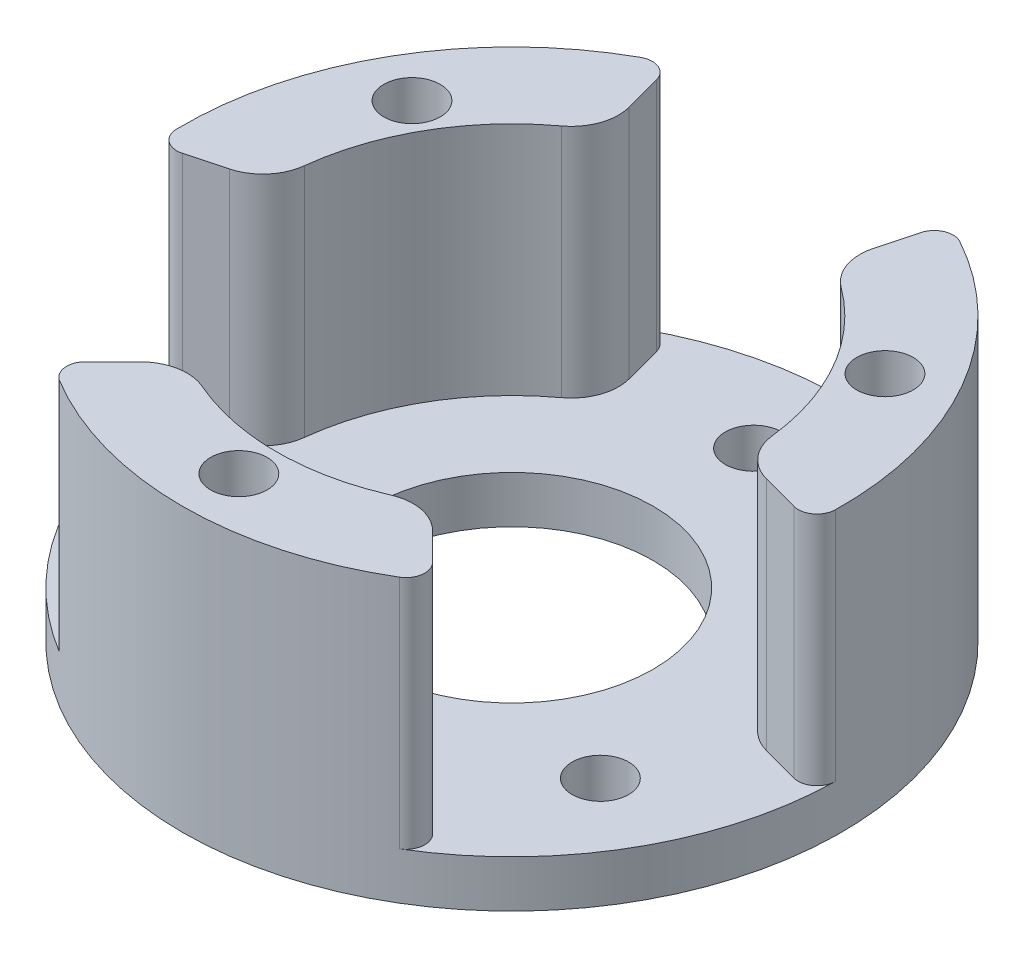
SolidWorks part; units mm, degrees
ref_plane "Front Plane" through (0, 0, 0) normal (0, 0, 1) x (1, 0, 0)
ref_plane "Top Plane" through (0, 0, 0) normal (0, 1, 0) x (1, 0, 0)
ref_plane "Right Plane" through (0, 0, 0) normal (1, 0, 0) x (0, 0, -1)
sketch "Sketch1" plane through (0, 0, 0) normal (0, 1, 0) x (1, 0, 0)
  line L0 (0, 25.66) -> (0, 0) construction
  line L1 (22.2222, -12.83) -> (0, 0) construction
  line L2 (-22.2222, -12.83) -> (0, 0) construction
  circle A0 centre (0, 0) radius 25.66 construction
  circle A1 centre (0, 0) radius 35
  circle A2 centre (0, 25.66) radius 3
  circle A3 centre (22.2222, -12.83) radius 3
  circle A4 centre (-22.2222, -12.83) radius 3
  circle A5 centre (0, 0) radius 15
  point P3 (0, 25.66)
  point P7 (22.2222, -12.83)
  point P9 (-22.2222, -12.83)
  point P11 (0, 0)
  point P18 (0, 0)
  dimension "D3" = 70
  dimension "D4" = 6
  dimension "D6" = 30
  dimension "D2" = 25.66
  dimension "D1" = 3
  dimension "D5" = 3
extrude "Boss-Extrude1" add sketch "Sketch1" along normal blind 5
sketch "Sketch2" plane through (0, 5, 0) normal (0, -1, 0) x (1, 0, 0)
  line L0 (0, 0) -> (0, 35) construction
  line L1 (15.5355, 23.9599) -> (20.1755, 28.5998)
  line L2 (-15.5355, 23.9599) -> (-20.1755, 28.5998)
  line L3 (28.5177, 1.4742) -> (34.8559, 3.1725)
  line L4 (12.9821, -25.4341) -> (14.6805, -31.7724)
  line L5 (-12.9821, -25.4341) -> (-14.6805, -31.7724)
  line L6 (-28.5177, 1.4742) -> (-34.8559, 3.1725)
  circle A0 centre (0, 0) radius 35 construction
  arc A1 (-20.1755, 28.5998) -> (20.1755, 28.5998) centre (0, 0) cw
  arc A2 (-10, 22.9129) -> (10, 22.9129) centre (0, 0) cw
  arc A3 (10, 22.9129) -> (15.5355, 23.9599) centre (12, 27.4955) ccw
  arc A4 (-10, 22.9129) -> (-15.5355, 23.9599) centre (-12, 27.4955) cw
  arc A5 (24.8431, -2.7962) -> (28.5177, 1.4742) centre (29.8118, -3.3554) cw
  arc A6 (34.8559, 3.1725) -> (14.6805, -31.7724) centre (0, 0) cw
  arc A7 (14.8431, -20.1167) -> (12.9821, -25.4341) centre (17.8118, -24.14) ccw
  arc A8 (24.8431, -2.7962) -> (14.8431, -20.1167) centre (0, 0) cw
  arc A9 (-14.8431, -20.1167) -> (-12.9821, -25.4341) centre (-17.8118, -24.14) cw
  arc A10 (-14.6805, -31.7724) -> (-34.8559, 3.1725) centre (0, 0) cw
  arc A11 (-24.8431, -2.7962) -> (-28.5177, 1.4742) centre (-29.8118, -3.3554) ccw
  arc A12 (-14.8431, -20.1167) -> (-24.8431, -2.7962) centre (0, 0) cw
  point P33 (0, 0)
  dimension "D1" = 5
  dimension "D2" = 25
  dimension "D3" = 45
  dimension "D4" = 20
  dimension "D5" = 3
extrude "Pegs" add sketch "Sketch2" against normal blind 24.9915
fillet "Fillet1" radius 2 6 edges at (-34.8559, 17.4958, 3.1725) (-14.6805, 17.4958, -31.7724) (14.6805, 17.4958, -31.7724) (34.8559, 17.4958, 3.1725) (20.1755, 17.4958, 28.5998) (-20.1755, 17.4958, 28.5998)
sketch "Sketch3" plane through (0, 0, 0) normal (0, -1, 0) x (1, 0, 0)
  line L0 (0, 0) -> (0, 29) construction
  line L1 (0, 0) -> (25.1147, -14.5) construction
  line L2 (0, 0) -> (-25.1147, -14.5) construction
  circle A0 centre (0, 0) radius 29 construction
  point P4 (0, 29)
  point P5 (25.1147, -14.5)
  point P7 (-25.1147, -14.5)
  point P8 (0, 0)
  dimension "D1" = 58
  dimension "D2" = 3
hole_wizard "Ø6.0mm Dowel Hole2" positions "Sketch3" profile "Sketch4" hole size "Ø6.0" standard "ANSI Metric" end condition through all
sketch "Sketch4" plane through (-25.1147, 0, -14.5) normal (1, 0, 0) x (0, 0, -1)
  line L0 (0, 0) -> (0, 29.9915)
  line L1 (0, 29.9915) -> (3, 29.9915)
  line L2 (3, 29.9915) -> (3, 0)
  line L5 (3, 0) -> (0, 0)
  line L11 (0, -6.35) -> (0, 107.95) construction
  dimension "Thru Hole Dia." = 6
  dimension "Thru Hole Depth" = 29.9915
